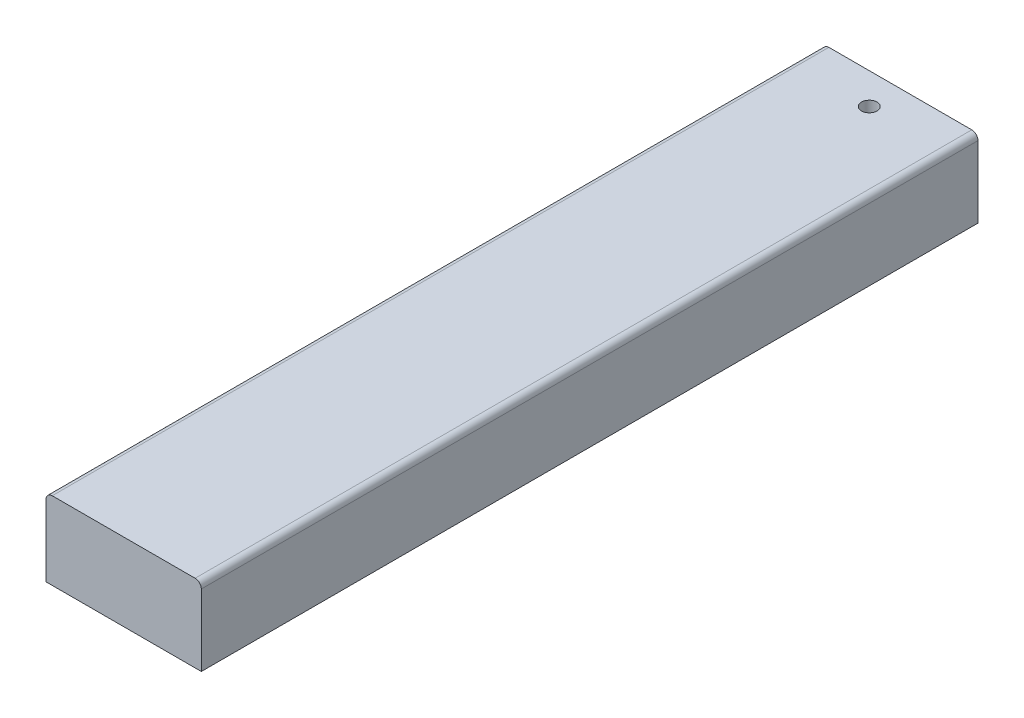
SolidWorks part; units mm, degrees
ref_plane "Front Plane" through (0, 0, 0) normal (0, 0, 1) x (1, 0, 0)
ref_plane "Top Plane" through (0, 0, 0) normal (0, 1, 0) x (1, 0, 0)
ref_plane "Right Plane" through (0, 0, 0) normal (1, 0, 0) x (0, 0, -1)
sketch "Sketch1" plane through (0, 0, 0) normal (0, 0, 1) x (1, 0, 0)
  line L1 (25, -10) -> (-25, -10)
  line L2 (25, -10) -> (25, 10)
  line L3 (25, 10) -> (-25, 10)
  line L4 (-25, -10) -> (-25, 10)
  line L5 (0, 10) -> (0, -10) construction
  line L6 (25, 0) -> (-25, 0) construction
  point P0 (0, 0)
  dimension "D1" = 20
  dimension "D2" = 50
extrude "Boss-Extrude1" add sketch "Sketch1" along normal mid plane 250
sketch "Sketch3" plane through (0, 10, 0) normal (0, 1, 0) x (1, 0, 0)
  line L0 (25, 125) -> (-25, 125) construction
  line L1 (25, 125) -> (-25, 125)
  line L2 (25, 125) -> (25, -125)
  line L3 (25, -125) -> (-25, -125)
  line L4 (-25, 125) -> (-25, -125)
  line L5 (0, -125) -> (0, 125) construction
  line L6 (25, 0) -> (-25, 0) construction
  point P0 (0, 0)
  dimension "D1" = 50
extrude "Boss-Extrude2" add sketch "Sketch3" along normal blind 5
ref_plane "Plane1" through (0, 15, 0) normal (0, 1, 0) x (1, 0, 0)
sketch "Sketch2" plane through (0, 15, 0) normal (0, 1, 0) x (1, 0, 0)
  line L1 (25, 125) -> (-25, 125) construction
  circle A0 centre (0, 115) radius 2.5
  dimension "D1" = 5
  dimension "D2" = 10
extrude "Cut-Extrude1" cut sketch "Sketch2" against normal blind 10 and the other way through all
fillet "Fillet1" radius 2 2 edges at (-25, 15, 0) (25, 15, 0)
sketch "Sketch4" plane through (0, -10, 0) normal (0, -1, 0) x (1, 0, 0)
  line L0 (-25, 125) -> (25, 125) construction
  line L5 (25, 125) -> (25, -125) construction
  circle A0 centre (0, 110) radius 7.874
  point P4 (0, 0)
  dimension "D2" = 15.748
  dimension "D1" = 15
  dimension "D3" = 25
extrude "Cut-Extrude2" cut sketch "Sketch4" against normal blind 5
